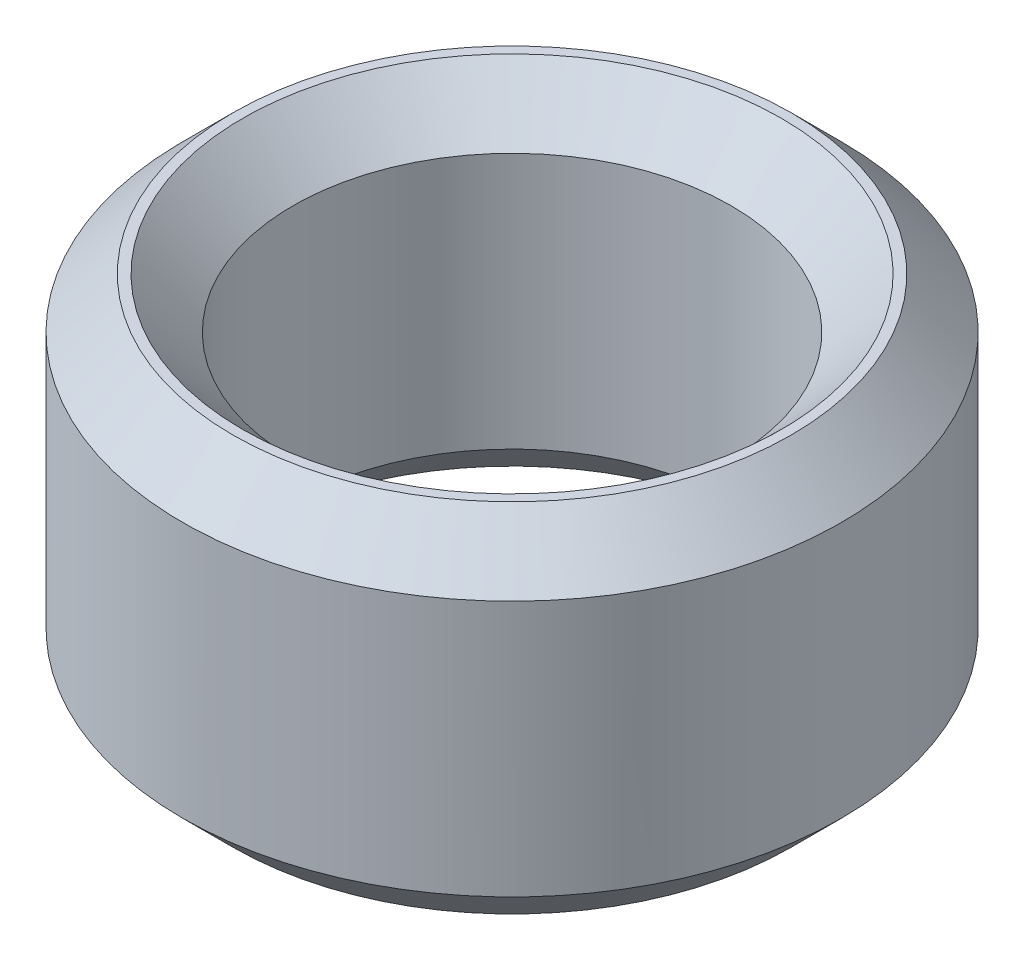
SolidWorks part; units mm, degrees
ref_plane "Front Plane" through (0, 0, 0) normal (0, 0, 1) x (1, 0, 0)
ref_plane "Top Plane" through (0, 0, 0) normal (0, 1, 0) x (1, 0, 0)
ref_plane "Right Plane" through (0, 0, 0) normal (1, 0, 0) x (0, 0, -1)
sketch "Sketch1" plane through (0, 0, 0) normal (0, 1, 0) x (1, 0, 0)
  circle A0 centre (0, 0) radius 20
  dimension "SLEEVE_OD" = 40
extrude "Boss-Extrude1" add sketch "Sketch1" along normal blind 21.6633
sketch "Sketch2" plane through (0, 0, 0) normal (0, 1, 0) x (1, 0, 0)
  circle A0 centre (0, 0) radius 13.2918
  dimension "BORE_D" = 26.5837
extrude "Cut-Extrude1" cut sketch "Sketch2" along normal through all
chamfer "Chamfer1" distance 3.06 angle 45 4 edges at (0, 21.6633, 13.2918) (0, 0, 13.2918) (0, 0, 20) (0, 21.6633, 20)
